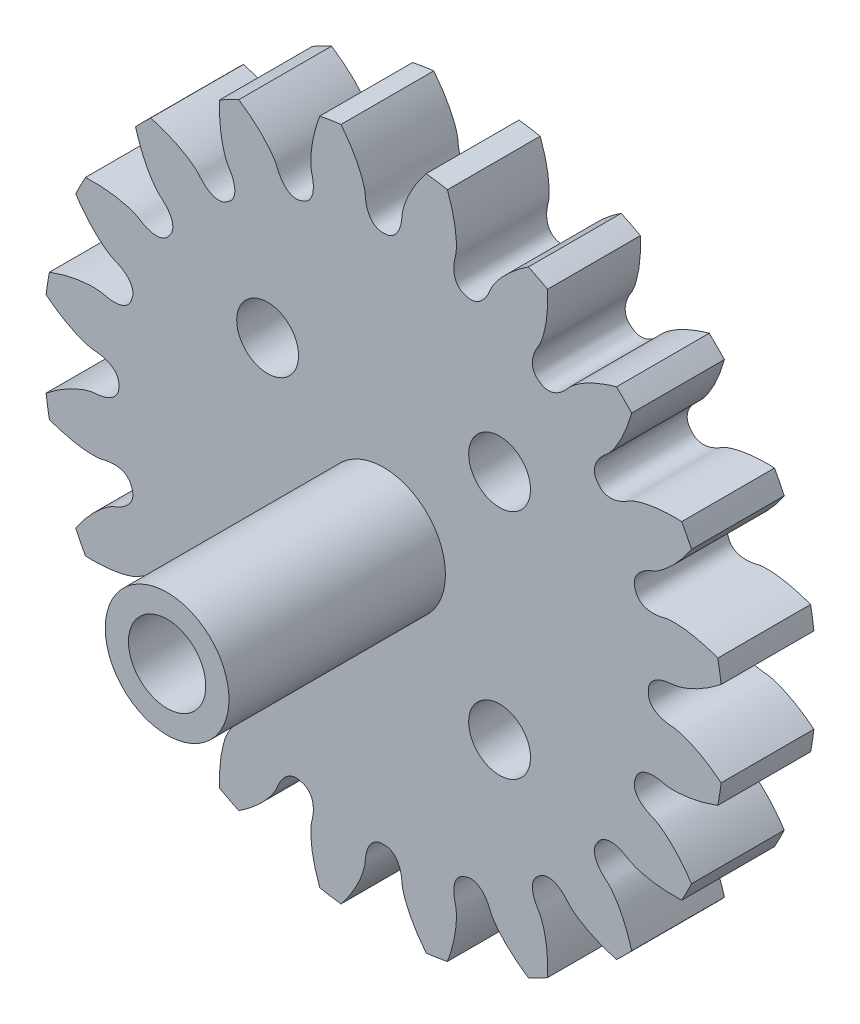
SolidWorks part; units mm, degrees
ref_plane "Front Plane" through (0, 0, 0) normal (0, 0, 1) x (1, 0, 0)
ref_plane "Top Plane" through (0, 0, 0) normal (0, 1, 0) x (1, 0, 0)
ref_plane "Right Plane" through (0, 0, 0) normal (1, 0, 0) x (0, 0, -1)
ref_axis "Axis1" through (0, 0, 55) along (0, 0, -1)
sketch "SketchRevolveSpurGear" plane through (0, 0, 0) normal (1, 0, 0) x (0, 0, -1)
  line L0 (0, 0) -> (1, 0) construction
  line L1 (-3, 0) -> (-3, 22)
  line L2 (-3, 22) -> (3, 22)
  line L3 (3, 22) -> (3, 0)
  line L4 (3, 0) -> (-3, 0)
  dimension "Side1" = 3
  dimension "OutsideRadius" = 22
  dimension "Side2" = 3
revolve "SpurGear" add sketch "SketchRevolveSpurGear" angle 360 about L0
sketch "SketchToothSpurGear" plane through (0, 0, 0) normal (0, 0, 1) x (1, 0, 0)
  arc A0 (21.9184, 2.8272) -> (21.9184, -2.8272) centre (0, 0) cw
  spline S0 degree 3 poles (21.9184, -2.8272) (21.7416, -2.6835) (21.4772, -2.4812) (21.1223, -2.2356) (20.8732, -2.0743) (20.6345, -1.9301) (20.4073, -1.8021) (20.1921, -1.6896) (19.9897, -1.5916) (19.8009, -1.5073) (19.6261, -1.4356) (19.4661, -1.3757) (19.3213, -1.3265) (19.1923, -1.2871) (19.0795, -1.2563) (18.9833, -1.2333) (18.9041, -1.2168) (18.8421, -1.206) (18.7324, -1.1899) (18.6208, -1.1888) (18.504, -1.1762) (18.4411, -1.1686) (18.3793, -1.1597) (18.3188, -1.1498) (18.2594, -1.1388) (18.2012, -1.1267) (18.1442, -1.1134) (18.0883, -1.099) (18.0336, -1.0835) (17.98, -1.0667) (17.9274, -1.0488) (17.8759, -1.0296) (17.8255, -1.0091) (17.7761, -0.9872) (17.7277, -0.9639) (17.6802, -0.939) (17.6338, -0.9125) (17.5883, -0.8842) (17.5438, -0.8541) (17.5003, -0.8219) (17.4579, -0.7874) (17.4167, -0.7505) (17.3768, -0.7109) (17.3383, -0.6684) (17.3015, -0.6229) (17.2668, -0.5742) (17.2346, -0.522) (17.2052, -0.4664) (17.1792, -0.4074) (17.1573, -0.3453) (17.1399, -0.2802) (17.1276, -0.2129) (17.1218, -0.1505) (17.1193, -0.0794) (17.1211, 0) (17.1193, 0.0794) (17.1218, 0.1505) (17.1276, 0.2129) (17.1399, 0.2802) (17.1573, 0.3453) (17.1792, 0.4074) (17.2052, 0.4664) (17.2346, 0.522) (17.2668, 0.5742) (17.3015, 0.6229) (17.3383, 0.6684) (17.3768, 0.7109) (17.4167, 0.7505) (17.4579, 0.7874) (17.5003, 0.8219) (17.5438, 0.8541) (17.5883, 0.8842) (17.6338, 0.9125) (17.6802, 0.939) (17.7277, 0.9639) (17.7761, 0.9872) (17.8255, 1.0091) (17.8759, 1.0296) (17.9274, 1.0488) (17.98, 1.0667) (18.0336, 1.0835) (18.0883, 1.099) (18.1442, 1.1134) (18.2012, 1.1267) (18.2594, 1.1388) (18.3188, 1.1498) (18.3793, 1.1597) (18.4411, 1.1686) (18.504, 1.1762) (18.6208, 1.1888) (18.7324, 1.1899) (18.8421, 1.206) (18.9041, 1.2168) (18.9833, 1.2333) (19.0795, 1.2563) (19.1923, 1.2871) (19.3213, 1.3265) (19.4661, 1.3757) (19.6261, 1.4356) (19.8009, 1.5073) (19.9897, 1.5916) (20.1921, 1.6896) (20.4073, 1.8021) (20.6345, 1.9301) (20.8732, 2.0743) (21.1223, 2.2356) (21.4772, 2.4812) (21.7416, 2.6835) (21.9184, 2.8272) knots 0 0 0 0 0.058197 0.084998 0.110268 0.134006 0.156213 0.176889 0.196032 0.213645 0.229725 0.244275 0.257292 0.268779 0.278733 0.287157 0.294048 0.299409 0.303237 0.322342 0.327835 0.333235 0.338546 0.343769 0.348909 0.353968 0.358951 0.363862 0.368706 0.373488 0.378214 0.38289 0.387524 0.392123 0.396695 0.401251 0.405801 0.410355 0.414927 0.41953 0.424177 0.428883 0.433664 0.438535 0.443509 0.448599 0.453816 0.459166 0.464651 0.470265 0.475996 0.481827 0.487732 0.491981 0.5 0.508019 0.512268 0.518173 0.524004 0.529735 0.535349 0.540834 0.546184 0.551401 0.556491 0.561465 0.566336 0.571117 0.575823 0.58047 0.585073 0.589645 0.594199 0.598749 0.603305 0.607877 0.612476 0.61711 0.621786 0.626512 0.631294 0.636138 0.641049 0.646032 0.651091 0.656231 0.661454 0.666765 0.672165 0.677658 0.696763 0.700591 0.705952 0.712843 0.721267 0.731221 0.742708 0.755725 0.770275 0.786355 0.803968 0.823111 0.843787 0.865994 0.889732 0.915002 0.941803 1 1 1 1
extrude "ToothExtrudeCutSpurGear" cut sketch "SketchToothSpurGear" against normal blind 3 and the other way blind 3
pattern_circular "PatternSpurGear" count 20 every 18 about axis through (0, 0, 55) along (0, 0, -1) of "ToothExtrudeCutSpurGear"
sketch "BoreRevolveSketch" plane through (0, 0, 0) normal (1, 0, 0) x (0, 0, -1)
  line L0 (0, 0) -> (1, 0) construction
  line L1 (-3, 0) -> (3, 0)
  line L2 (3, 0) -> (3, 4)
  line L3 (3, 4) -> (-3, 4)
  line L4 (-3, 4) -> (-3, 0)
  dimension "BoreSide1" = 3
  dimension "TaperSide1" = 4
  dimension "BoreSide2" = 3
  dimension "TaperSide2" = 4
revolve "BoreRevolveCut" cut sketch "BoreRevolveSketch" angle 360 about L0
sketch "AuxiliarySketchSpurGear" plane through (0, 0, 0) normal (0, 0, 1) x (1, 0, 0)
  circle A0 centre (0, 0) radius 20 construction
  circle A1 centre (0, 0) radius 18.7939 construction
  circle A2 centre (0, 0) radius 18.7991 construction
  circle A3 centre (0, 0) radius 22 construction
  circle A4 centre (0, 0) radius 17.1204 construction
  dimension "PitchDiameter" = 40
  dimension "BaseDiameter" = 37.5877
  dimension "FormDiameter" = 37.5983
  dimension "MajorDiameter" = 44
  dimension "MinorDiameter" = 34.2408
sketch "Sketch1" plane through (0, 0, -3) normal (0, 0, -1) x (-1, 0, 0)
  circle A0 centre (0, 0) radius 4
  circle A1 centre (0, 0) radius 2.5
extrude "Boss-Extrude1" add sketch "Sketch1" against normal blind 20
sketch "Sketch2" plane through (0, 0, -3) normal (0, 0, -1) x (-1, 0, 0)
  line L0 (-7.5, 7.5) -> (-7.5, -7.5) construction
  line L1 (-7.5, 7.5) -> (7.5, -7.5) construction
  line L2 (7.5, 7.5) -> (-7.5, -7.5) construction
  line L3 (-7.5, -7.5) -> (7.5, -7.5) construction
  line L4 (7.5, -7.5) -> (7.5, 7.5) construction
  line L5 (7.5, 7.5) -> (-7.5, 7.5) construction
  circle A0 centre (7.5, 7.5) radius 2
  circle A1 centre (7.5, -7.5) radius 2
  circle A2 centre (-7.5, -7.5) radius 2
  circle A3 centre (-7.5, 7.5) radius 2
  point P0 (0, 0)
  dimension "D3" = 4
  dimension "D4" = 4
  dimension "D5" = 4
  dimension "D6" = 4
  dimension "D1" = 15
  dimension "D2" = 15
extrude "Cut-Extrude1" cut sketch "Sketch2" against normal blind 6
